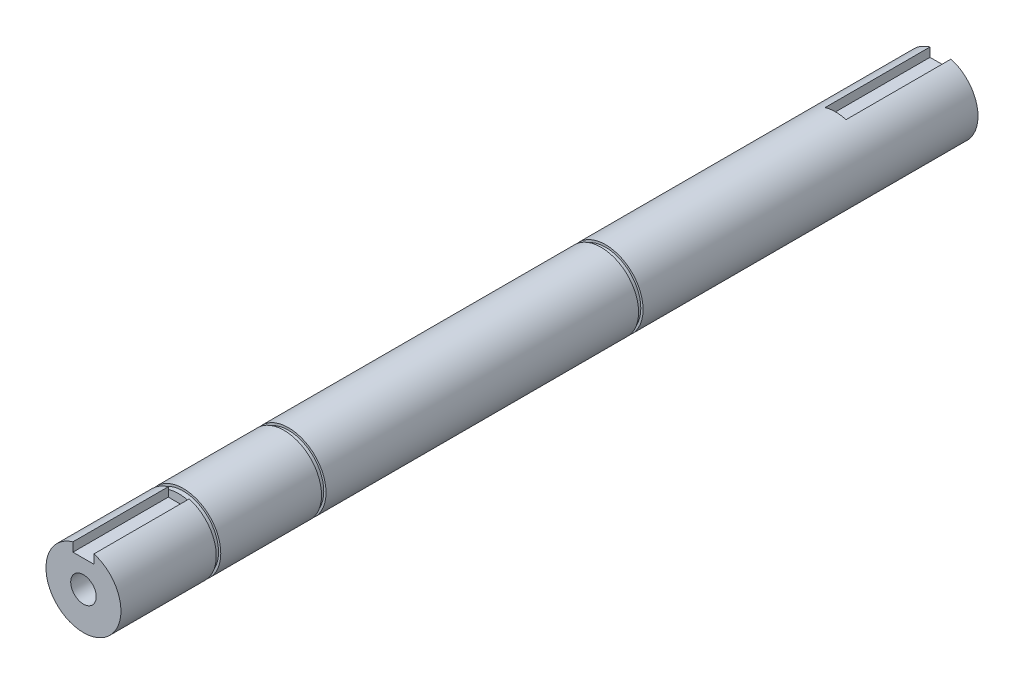
SolidWorks part; units mm, degrees
note: The reader was unsure of these and kept them because the rebuilt part matched: shared geometry of "Эскиз6<2>".
material "AISI 1020"
ref_plane "Спереди" through (0, 0, 0) normal (0, 0, 1) x (1, 0, 0)
ref_plane "Сверху" through (0, 0, 0) normal (0, 1, 0) x (1, 0, 0)
ref_plane "Справа" through (0, 0, 0) normal (1, 0, 0) x (0, 0, -1)
sketch "Эскиз1" plane through (0, 0, 0) normal (0, 0, 1) x (1, 0, 0)
  circle A0 centre (0, 0) radius 12.5
  dimension "D1" = 25
extrude "Бобышка-Вытянуть1" add sketch "Эскиз1" along normal blind 5 and the other way up to surface (280.8363 mm away)
hole_wizard "Отверстие обработанное метчиком M101" positions "Эскиз4" profile "Эскиз5" tap size "M10" standard "ISO"
sketch "Эскиз4" plane through (0, 0, -280.8363) normal (0, 0, -1) x (-1, 0, 0)
  point P0 (0, 0)
sketch "Эскиз5" plane through (0, 0, -280.8363) normal (1, 0, 0) x (0, 1, 0)
  line L0 (0, 0) -> (0, 30.0537)
  line L1 (0, 30.0537) -> (4.25, 27.5)
  line L2 (4.25, 27.5) -> (4.25, 0)
  line L5 (4.25, 0) -> (0, 0)
  line L10 (0, 30.0537) -> (-4.25, 27.5) construction
  line L11 (0, -6.35) -> (0, 107.95) construction
  dimension "Диаметр сверла" = 8.5
  dimension "Глубина сверла" = 27.5
  dimension "Угол заточки сверла" = 118
cosmetic thread "Отверстие резьбы1" parameters "D1"=20, "D2"=10
sketch "Эскиз6" plane through (0, 0, -280.8363) normal (0, 0, -1) x (-1, 0, 0)
  line L0 (-3.5, 12.5) -> (3.5, 12.5) construction
  line L1 (-3.5, 16) -> (3.5, 16)
  line L2 (-3.5, 16) -> (-3.5, 9)
  line L3 (-3.5, 9) -> (3.5, 9)
  line L4 (3.5, 16) -> (3.5, 9)
  circle A0 centre (0, 0) radius 12.5 construction
  point P8 (0, 16)
  dimension "D1" = 7
extrude "Вырез-Вытянуть1" cut sketch "Эскиз6" against normal blind 35
sketch "Эскиз7" plane through (0, 0, 0) normal (1, 0, 0) x (0, 0, -1)
  line L0 (-1000, 0) -> (49000, 0) construction
  line L2 (63.4, -12.3111) -> (63.4, 14.6811) construction
  line L3 (63.4, 11.75) -> (61.9, 11.75)
  line L4 (63.4, 11.75) -> (63.4, 14.5)
  line L5 (63.4, 14.5) -> (61.9, 14.5)
  line L6 (61.9, 11.75) -> (61.9, 14.5)
  line L7 (63.4, 11.75) -> (62.2, 11.75) construction
  line L8 (245.8363, 12.5) -> (-5, 12.5) construction
  line L9 (62.2, -17.4) -> (62.2, 17.4) construction
  line L10 (28, 16.45) -> (28, -16.45) construction
  line L11 (26.8, 11.75) -> (28.3, 11.75)
  line L12 (26.8, 11.75) -> (26.8, 14.5)
  line L13 (26.8, 14.5) -> (28.3, 14.5)
  line L14 (28.3, 11.75) -> (28.3, 14.5)
  line L15 (168.8363, 40) -> (168.8363, -40) construction
  line L16 (167.6363, 14.5) -> (169.1363, 14.5)
  line L17 (167.6363, 14.5) -> (167.6363, 11.75)
  line L18 (167.6363, 11.75) -> (169.1363, 11.75)
  line L19 (169.1363, 14.5) -> (169.1363, 11.75)
  dimension "D1" = 1.5
  dimension "D2" = 2
  dimension "D3" = 1.2
  dimension "D4" = 1.2
  dimension "D5" = 1.2
revolve "Вырез-Повернуть1" cut sketch "Эскиз7" angle 360 about L0
extrude "Вырез-Вытянуть2" cut sketch "Эскиз6<2>" along normal up to surface (31.8 mm away) from surface at -285.8363 starting at face at (12.5, 0, 5)
sketch "Эскиз6<2>" plane through (0, 0, -280.8363) normal (0, 0, -1) x (-1, 0, 0) same geometry as "Эскиз6"
hole_wizard "Отверстие обработанное метчиком M102" positions "Эскиз9" profile "Эскиз10" tap size "M10" standard "ISO"
sketch "Эскиз9" plane through (0, 0, 5) normal (0, 0, 1) x (1, 0, 0)
  point P0 (0, 0)
sketch "Эскиз10" plane through (0, 0, 5) normal (1, 0, 0) x (0, -1, 0)
  line L0 (0, 0) -> (0, 30.0537)
  line L1 (0, 30.0537) -> (4.25, 27.5)
  line L2 (4.25, 27.5) -> (4.25, 0)
  line L5 (4.25, 0) -> (0, 0)
  line L10 (0, 30.0537) -> (-4.25, 27.5) construction
  line L11 (0, -6.35) -> (0, 107.95) construction
  dimension "Диаметр сверла" = 8.5
  dimension "Глубина сверла" = 27.5
  dimension "Угол заточки сверла" = 118
cosmetic thread "Отверстие резьбы2" parameters "D1"=20, "D2"=10
